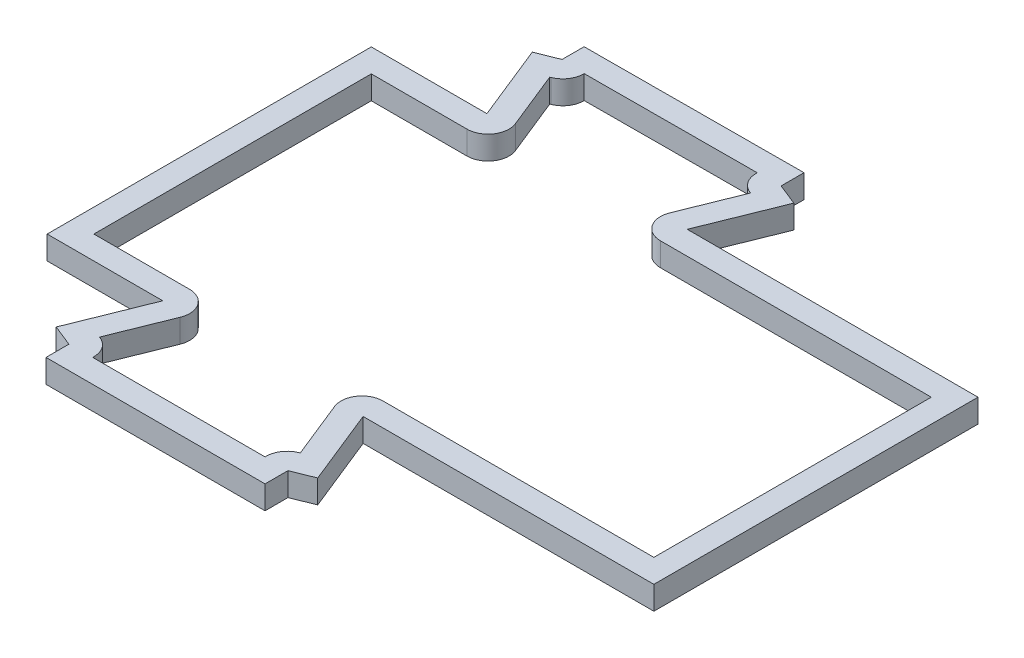
SolidWorks part; units mm, degrees
ref_plane "Front Plane" through (0, 0, 0) normal (0, 0, 1) x (1, 0, 0)
ref_plane "Top Plane" through (0, 0, 0) normal (0, 1, 0) x (1, 0, 0)
ref_plane "Right Plane" through (0, 0, 0) normal (1, 0, 0) x (0, 0, -1)
ref_axis "Axis1" through (-33.0333, 0, 0) along (1, 0, 0)
ref_axis "Axis2" through (0, 24.5224, 0) along (0, -1, 0)
ref_axis "Axis3" through (0, 0, -30.7663) along (0, 0, 1)
sketch "Sketch1" plane through (0, 0, 0) normal (0, 1, 0) x (1, 0, 0)
  line L0 (-33, 0) -> (33, 0) construction
  line L1 (-33, -70) -> (33, -70) construction
  line L2 (-33, -70) -> (-33, 70) construction
  line L3 (-33, 70) -> (33, 70) construction
  line L4 (33, -70) -> (33, 70) construction
  line L5 (-33, 70) -> (-73, 70) construction
  line L6 (-73, 70) -> (-73, -70) construction
  line L7 (-73, -70) -> (-33, -70) construction
  line L8 (33, 70) -> (73, 70) construction
  line L9 (73, 70) -> (73, -70) construction
  line L10 (73, -70) -> (33, -70) construction
  line L11 (73, 70) -> (168, 70) construction
  line L12 (168, 70) -> (168, -70) construction
  line L13 (168, -70) -> (73, -70) construction
  line L14 (-33, 70) -> (-47.5, 106) construction
  line L15 (-47.5, 106) -> (47.5, 106) construction
  line L16 (47.5, 106) -> (33, 70) construction
  line L17 (-33, -70) -> (-47.5, -106) construction
  line L18 (-47.5, -106) -> (47.5, -106) construction
  line L19 (47.5, -106) -> (33, -70) construction
  line L20 (-47.5, 106) -> (-47.5, 116) construction
  line L21 (-47.5, 116) -> (47.5, 116) construction
  line L22 (47.5, 116) -> (47.5, 106) construction
  line L23 (-47.5, -106) -> (-47.5, -116) construction
  line L24 (-47.5, -116) -> (47.5, -116) construction
  line L25 (47.5, -116) -> (47.5, -106) construction
  line L26 (-47.5, 106) -> (-56.7759, 102.2639) construction
  line L27 (-56.7759, 102.2639) -> (-43.7807, 70) construction
  line L28 (47.5, 106) -> (56.7759, 102.2639) construction
  line L29 (56.7759, 102.2639) -> (43.7807, 70) construction
  line L30 (-47.5, -106) -> (-56.7759, -102.2639) construction
  line L31 (-56.7759, -102.2639) -> (-43.7807, -70) construction
  line L32 (47.5, -106) -> (56.7759, -102.2639) construction
  line L33 (56.7759, -102.2639) -> (43.7807, -70) construction
  line L34 (-73, 70) -> (-93, 70) construction
  line L35 (-93, 70) -> (-93, -70) construction
  line L36 (-93, -70) -> (-73, -70) construction
  point P0 (0, 0)
  dimension "D1" = 66
  dimension "D2" = 140
  dimension "D3" = 40
  dimension "D4" = 40
  dimension "D5" = 95
  dimension "D6" = 95
  dimension "D7" = 36
  dimension "D8" = 10
  dimension "D9" = 20
sketch "Sketch2" plane through (0, 0, 0) normal (0, 1, 0) x (1, 0, 0)
  line L0 (-93, 70) -> (-43.7807, 70) construction
  line L1 (-43.7807, 70) -> (-56.7759, 102.2639) construction
  line L2 (-56.7759, 102.2639) -> (-47.5, 106) construction
  line L3 (-47.5, 106) -> (-47.5, 115.6287) construction
  line L4 (-47.5, 106) -> (-47.5, 116) construction
  line L5 (-47.5, 115.6287) -> (47.5, 116) construction
  line L6 (47.5, 116) -> (47.5, 106) construction
  line L7 (47.5, 106) -> (56.7759, 102.2639) construction
  line L8 (56.7759, 102.2639) -> (43.7807, 70) construction
  line L9 (43.7807, 70) -> (168, 70) construction
  line L10 (168, 70) -> (168, -70) construction
  line L11 (168, -70) -> (43.7807, -70) construction
  line L12 (43.7807, -70) -> (56.7759, -102.2639) construction
  line L13 (56.7759, -102.2639) -> (47.5, -106) construction
  line L14 (47.5, -106) -> (47.5, -116) construction
  line L15 (47.5, -116) -> (-47.5, -116) construction
  line L16 (-47.5, -116) -> (-47.5, -106) construction
  line L17 (-47.5, -106) -> (-56.7759, -102.2639) construction
  line L18 (-56.7759, -102.2639) -> (-43.7807, -70) construction
  line L19 (-43.7807, -70) -> (-93, -70) construction
  line L20 (-93, -70) -> (-93, 70) construction
  line L21 (-92.4, -69.4) -> (-92.4, 69.4)
  line L22 (-92.4, 69.4) -> (-42.8922, 69.4)
  line L23 (-42.8922, 69.4) -> (-55.9951, 101.9315)
  line L24 (-55.9951, 101.9315) -> (-46.9, 105.5948)
  line L25 (-46.9, 105.5948) -> (-46.9, 115.031)
  line L26 (-46.9, 115.031) -> (46.9, 115.3977)
  line L27 (46.9, 115.3977) -> (46.9, 105.5948)
  line L28 (46.9, 105.5948) -> (55.9951, 101.9315)
  line L29 (55.9951, 101.9315) -> (42.8922, 69.4)
  line L30 (42.8922, 69.4) -> (167.4, 69.4)
  line L31 (167.4, 69.4) -> (167.4, -69.4)
  line L32 (167.4, -69.4) -> (42.8922, -69.4)
  line L33 (42.8922, -69.4) -> (55.9951, -101.9315)
  line L34 (55.9951, -101.9315) -> (46.9, -105.5948)
  line L35 (46.9, -105.5948) -> (46.9, -115.4)
  line L36 (46.9, -115.4) -> (-46.9, -115.4)
  line L37 (-46.9, -115.4) -> (-46.9, -105.5948)
  line L38 (-46.9, -105.5948) -> (-55.9951, -101.9315)
  line L39 (-55.9951, -101.9315) -> (-42.8922, -69.4)
  line L40 (-42.8922, -69.4) -> (-92.4, -69.4)
  line L41 (-82.4, -59.4) -> (-82.4, 59.4)
  line L42 (-82.4, 59.4) -> (-28.0837, 59.4)
  line L43 (-28.0837, 59.4) -> (-42.9832, 96.3918)
  line L44 (-42.9832, 96.3918) -> (-36.9, 98.8419)
  line L45 (-36.9, 98.8419) -> (-36.9, 105.07)
  line L46 (-36.9, 105.07) -> (36.9, 105.3585)
  line L47 (36.9, 105.3585) -> (36.9, 98.8419)
  line L48 (36.9, 98.8419) -> (42.9832, 96.3918)
  line L49 (42.9832, 96.3918) -> (28.0837, 59.4)
  line L50 (28.0837, 59.4) -> (157.4, 59.4)
  line L51 (157.4, 59.4) -> (157.4, -59.4)
  line L52 (157.4, -59.4) -> (28.0837, -59.4)
  line L53 (28.0837, -59.4) -> (42.9832, -96.3918)
  line L54 (42.9832, -96.3918) -> (36.9, -98.8419)
  line L55 (36.9, -98.8419) -> (36.9, -105.4)
  line L56 (36.9, -105.4) -> (-36.9, -105.4)
  line L57 (-36.9, -105.4) -> (-36.9, -98.8419)
  line L58 (-36.9, -98.8419) -> (-42.9832, -96.3918)
  line L59 (-42.9832, -96.3918) -> (-28.0837, -59.4)
  line L60 (-28.0837, -59.4) -> (-82.4, -59.4)
  dimension "D1" = 0.6
  dimension "D2" = 10
extrude "Boss-Extrude2" add sketch "Sketch2" along normal blind 10
fillet "Fillet2" radius 9 8 edges at (36.9, 5, 98.8419) (-36.9, 5, 98.8419) (28.0837, 5, 59.4) (-28.0837, 5, 59.4) (36.9, 5, -98.8419) (28.0837, 5, -59.4) (-36.9, 5, -98.8419) (-28.0837, 5, -59.4)
